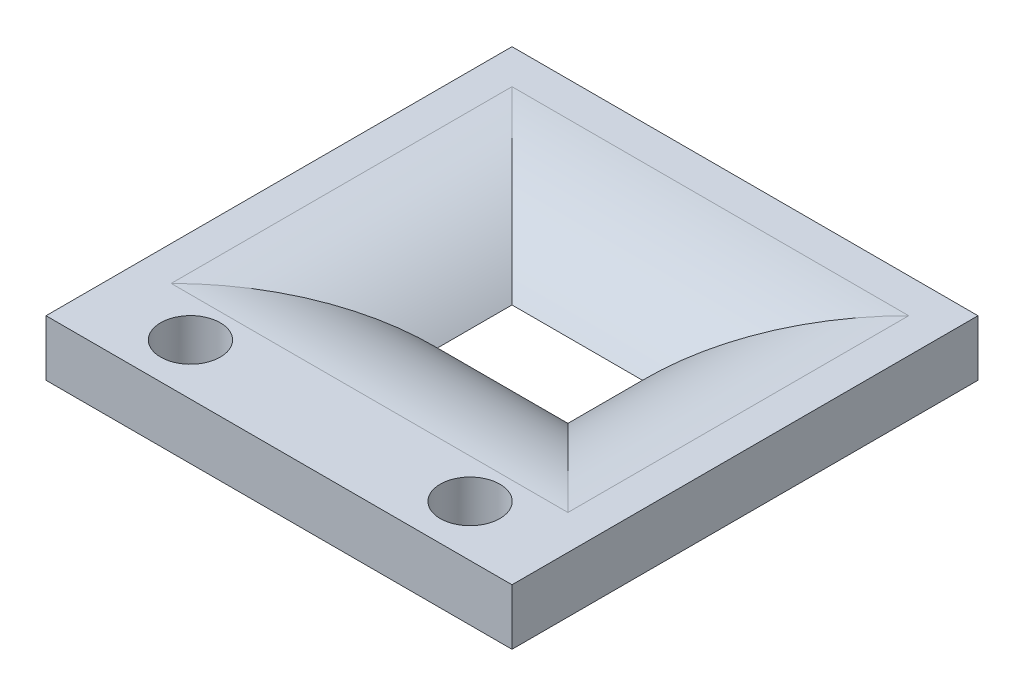
SolidWorks part; units mm, degrees
ref_plane "Front" through (0, 0, 0) normal (0, 0, 1) x (1, 0, 0)
ref_plane "Top" through (0, 0, 0) normal (0, 1, 0) x (1, 0, 0)
ref_plane "Right" through (0, 0, 0) normal (1, 0, 0) x (0, 0, -1)
sketch "Sketch1" plane through (0, 0, 0) normal (0, 1, 0) x (1, 0, 0)
  line L1 (-12.5, -12.5) -> (12.5, -12.5)
  line L2 (-12.5, -12.5) -> (-12.5, 12.5)
  line L3 (-12.5, 12.5) -> (12.5, 12.5)
  line L4 (12.5, -12.5) -> (12.5, 12.5)
  line L5 (-12.5, -12.5) -> (12.5, 12.5) construction
  line L6 (-12.5, 12.5) -> (12.5, -12.5) construction
  point P0 (0, 0)
  dimension "D1" = 25
  dimension "D2" = 25
extrude "Boss-Extrude1" add sketch "Sketch1" along normal blind 3
sketch "Sketch2" plane through (0, 3, 0) normal (0, 1, 0) x (1, 0, 0)
  line L0 (-12.5, -9.75) -> (12.5, -9.75) construction
  line L1 (-12.5, 12.5) -> (-12.5, -12.5) construction
  line L2 (12.5, -12.5) -> (12.5, 12.5) construction
  line L4 (-12.5, -12.5) -> (12.5, -12.5) construction
  point P6 (7.5, -9.75)
  point P9 (-7.5, -9.75)
  dimension "D1" = 2.75
  dimension "D2" = 5
  dimension "D3" = 5
hole_wizard "M3 Clearance Hole1" positions "3DSketch1" profile "Sketch3" hole size "M3" standard "ANSI Metric"
sketch3d "3DSketch1"
  point P0 (-7.5, 3, 9.75)
  point P3 (7.5, 3, 9.75)
sketch "Sketch3" plane through (-7.5, 3, 9.75) normal (1, 0, 0) x (0, 0, 1)
  line L0 (0, 0) -> (0, 5.9614)
  line L1 (0, 5.9614) -> (1.6, 5)
  line L2 (1.6, 5) -> (1.6, 0)
  line L5 (1.6, 0) -> (0, 0)
  line L10 (0, 5.9614) -> (-1.6, 5) construction
  line L11 (0, -6.35) -> (0, 107.95) construction
  dimension "Hole Dia." = 3.2
  dimension "Hole Depth" = 5
  dimension "Drill Angle" = 118
sketch "Sketch4" plane through (0, 3, 0) normal (0, 1, 0) x (1, 0, 0)
  line L0 (-12.5, 12.5) -> (0, 12.5) construction
  line L1 (12.5, 12.5) -> (-12.5, 12.5) construction
  line L2 (0, 12.5) -> (0, 1.5) construction
  line L4 (-3.5, -0.5) -> (3.5, -0.5)
  line L5 (-3.5, -0.5) -> (-3.5, 3.5)
  line L6 (-3.5, 3.5) -> (3.5, 3.5)
  line L7 (3.5, -0.5) -> (3.5, 3.5)
  line L8 (-3.5, -0.5) -> (3.5, 3.5) construction
  line L9 (-3.5, 3.5) -> (3.5, -0.5) construction
  dimension "D1" = 12.5
  dimension "D2" = 11
  dimension "D3" = 7
  dimension "D4" = 4
extrude "Cut-Extrude1" cut sketch "Sketch4" against normal up to surface (3 mm away) up to face at (-7.5, 0, 8.15)
fillet "Fillet2" radius 10 4 edges at (3.5, 3, -1.5) (-3.5, 3, -1.5) (0, 3, -3.5) (0, 3, 0.5)
